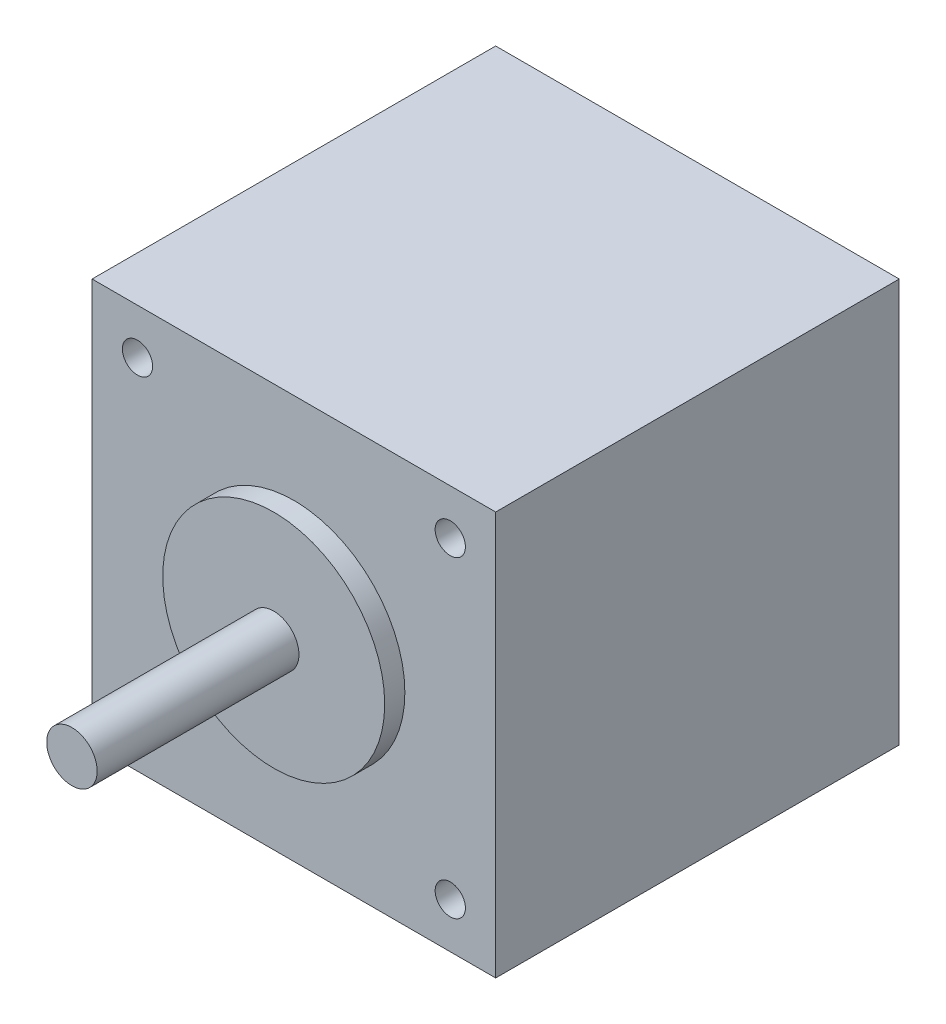
SolidWorks part; units mm, degrees
ref_plane "Front Plane" through (0, 0, 0) normal (0, 0, 1) x (1, 0, 0)
ref_plane "Top Plane" through (0, 0, 0) normal (0, 1, 0) x (1, 0, 0)
ref_plane "Right Plane" through (0, 0, 0) normal (1, 0, 0) x (0, 0, -1)
sketch "Sketch1" plane through (0, 0, 0) normal (0, 0, 1) x (1, 0, 0)
  line L1 (20, 20) -> (-20, 20)
  line L2 (20, 20) -> (20, -20)
  line L3 (20, -20) -> (-20, -20)
  line L4 (-20, 20) -> (-20, -20)
  line L5 (20, 20) -> (-20, -20) construction
  line L6 (20, -20) -> (-20, 20) construction
  point P0 (0, 0)
  dimension "D1" = 40
  dimension "D2" = 40
extrude "Boss-Extrude1" add sketch "Sketch1" along normal blind 40
sketch "Sketch2" plane through (0, 0, 40) normal (0, 0, 1) x (1, 0, 0)
  circle A0 centre (0, 0) radius 11
  dimension "D1" = 22
extrude "Boss-Extrude2" add sketch "Sketch2" along normal blind 2
sketch "Sketch3" plane through (0, 0, 42) normal (0, 0, 1) x (1, 0, 0)
  circle A0 centre (0, 0) radius 2.5
  dimension "D1" = 5
extrude "Boss-Extrude3" add sketch "Sketch3" along normal blind 20
sketch "Sketch4" plane through (0, 0, 40) normal (0, 0, 1) x (1, 0, 0)
  line L0 (0, 19.189) -> (0, -16.1449) construction
  line L1 (-16.7972, 0) -> (17.1233, 0) construction
  circle A0 centre (-15.5, 15.5) radius 1.5
  circle A2 centre (-15.5, -15.5) radius 1.5
  circle A3 centre (15.5, -15.5) radius 1.5
  circle A4 centre (15.5, 15.5) radius 1.5
  dimension "D1" = 3
  dimension "D2" = 31
  dimension "D3" = 15.5
extrude "Cut-Extrude1" cut sketch "Sketch4" against normal through all contours A0 | A2 | A4
extrude "Cut-Extrude2" cut sketch "Sketch4<3>" along direction (0, 0, -1) on the side against the normal through all
sketch "Sketch4<3>" plane through (0, 0, 40) normal (0, 0, 1) x (1, 0, 0) same geometry as "Sketch4"
